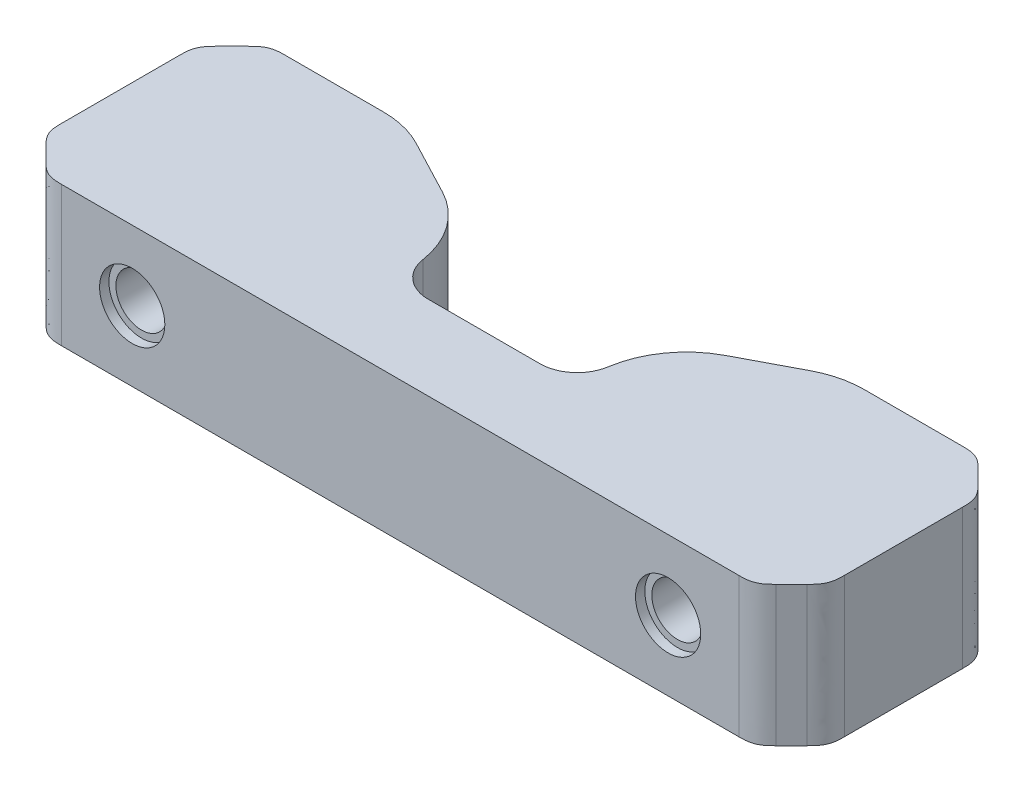
SolidWorks part; units mm, degrees
ref_plane "Plan de face" through (0, 0, 0) normal (0, 0, 1) x (1, 0, 0)
ref_plane "Plan de dessus" through (0, 0, 0) normal (0, 1, 0) x (1, 0, 0)
ref_plane "Plan de droite" through (0, 0, 0) normal (1, 0, 0) x (0, 0, -1)
sketch "Esquisse1" plane through (0, 0, 0) normal (0, 1, 0) x (1, 0, 0)
  line L9 (-42, 8) -> (-42, 0)
  line L10 (-42, 0) -> (-42, -8)
  line L11 (-42, -8) -> (-38, -8) construction
  line L12 (-38, -8) -> (-38, -12) construction
  line L19 (-22, 12) -> (-14, 18)
  line L20 (-38, -12) -> (-42, -8)
  line L22 (0, 0) -> (0, 20) construction
  line L23 (0, 0) -> (0, -12) construction
  line L24 (-30, 0) -> (1, 0) construction
  line L25 (0, -55) -> (0, 55) construction
  line L26 (-10, -3) -> (10, -3)
  line L36 (0, 20) -> (0, 9) construction
  line L42 (0, -12) -> (0, 18) construction
  line L45 (-10, 9) -> (-10, -3)
  line L56 (-10, 9) -> (10, 9)
  line L57 (-14, 18) -> (14, 18)
  line L58 (22, 12) -> (14, 18)
  line L59 (38, 8) -> (38, 12) construction
  line L60 (42, 8) -> (38, 8) construction
  line L61 (42, 8) -> (38, 12)
  line L62 (38, 12) -> (22, 12)
  line L63 (42, 8) -> (42, 0)
  line L64 (10, 9) -> (10, -3)
  line L71 (-42, 8) -> (-38, 8) construction
  line L72 (-38, 8) -> (-38, 12) construction
  line L73 (-38, -12) -> (38, -12)
  line L74 (-38, 12) -> (-22, 12)
  line L75 (-42, 8) -> (-38, 12)
  line L76 (38, -8) -> (38, -12) construction
  line L77 (42, -8) -> (38, -8) construction
  line L78 (38, -12) -> (42, -8)
  line L79 (42, 0) -> (42, -8)
  circle A0 centre (-30, 0) radius 4.2
  circle A3 centre (30, 0) radius 4.2
  point P36 (0, -3)
  point P39 (0, -3)
  dimension "D4" = 4
  dimension "D5" = 8.4
  dimension "D6" = 4
  dimension "D15" = 30
  dimension "D2" = 8
  dimension "D3" = 8
  dimension "D7" = 14
  dimension "D8" = 9
  dimension "D11" = 9
  dimension "D13" = 10
extrude "Boss.-Extru.1" add sketch "Esquisse1" along normal blind 15 contours L19 L9 L10 L56 L64 L26 L45 A0 | A0 | A3 region at (-39.3693, 0, -9.3693) region at (-30, 0, 0) region at (30, 0, 0)
fillet "Congé1" radius 4 12 edges at (42, 7.5, 8) (38, 7.5, 12) (42, 7.5, -8) (38, 7.5, -12) (22, 7.5, -12) (14, 7.5, -18) (-14, 7.5, -18) (-22, 7.5, -12) (-38, 7.5, -12) (-42, 7.5, -8) (-42, 7.5, 8) (-38, 7.5, 12) curvature continuous yes
extrude "Enlèv. mat.-Extru.1" cut sketch "Esquisse1<4>" along normal blind 12 contours A0 | A3 region at (-30, 0, 0) region at (30, 0, 0)
sketch "Esquisse1<4>" plane through (0, 0, 0) normal (0, 1, 0) x (1, 0, 0) same geometry as "Esquisse1"
fillet "Congé2" radius 4 4 edges at (10, 7.5, 3) (-10, 7.5, 3) (10, 7.5, -9) (-10, 7.5, -9)
sketch "Esquisse2" plane through (0, 0, 12) normal (0, 0, 1) x (1, 0, 0)
  line L0 (0, 0) -> (0, 15) construction
  line L2 (26, 7.5) -> (-26, 7.5) construction
  line L3 (-36.3431, 15) -> (36.3431, 15) construction
  line L4 (0, -55) -> (0, 55) construction
  line L5 (26, 7.5) -> (31.5, 7.5) construction
  circle A0 centre (-28.75, 7.5) radius 2.75
  circle A1 centre (28.75, 7.5) radius 2.75
  point P14 (0, 7.5)
  dimension "D2" = 5.5
  dimension "D1" = 26
extrude "Enlèv. mat.-Extru.2" cut sketch "Esquisse2" against normal blind 10 and the other way through all
sketch "Esquisse4" plane through (0, 0, 12) normal (0, 0, 1) x (1, 0, 0)
  line L0 (26, 7.5) -> (31.5, 7.5) construction
  arc A0 (26.3068, 8.7622) -> (26.3068, 6.2378) centre (28.75, 7.5) ccw construction
  arc A1 (26.3068, 6.2378) -> (26.3068, 8.7622) centre (28.75, 7.5) ccw construction
  circle A2 centre (28.75, 7.5) radius 3.5
  dimension "D1" = 7
extrude "Enlèv. mat.-Extru.3" cut sketch "Esquisse4" against normal blind 1
sketch "Esquisse5" plane through (0, 0, 12) normal (0, 0, 1) x (1, 0, 0)
  line L0 (-28.75, 10.25) -> (-28.75, 4.75) construction
  circle A0 centre (-28.75, 7.5) radius 2.75 construction
  arc A1 (-26.3068, 8.7622) -> (-26.3068, 6.2378) centre (-28.75, 7.5) ccw construction
  circle A2 centre (-28.75, 7.5) radius 3.5
  dimension "D1" = 7
extrude "Enlèv. mat.-Extru.4" cut sketch "Esquisse5" against normal blind 1
sketch "Esquisse6" plane through (0, 0, 0) normal (0, -1, 0) x (1, 0, 0)
  line L0 (-23.3333, -12) -> (-10, -5)
  line L1 (-10, -5) -> (10, -5)
  line L2 (10, -5) -> (23.3333, -12)
  line L3 (23.3333, -12) -> (23.3333, -18)
  line L4 (23.3333, -18) -> (-23.3333, -18)
  line L5 (-23.3333, -18) -> (-23.3333, -12)
  line L6 (-12.6667, -18) -> (12.6667, -18) construction
extrude "Enlèv. mat.-Extru.5" cut sketch "Esquisse6" against normal through all
fillet "Congé3" radius 10 4 edges at (-10, 7.5, -5) (10, 7.5, -5)
